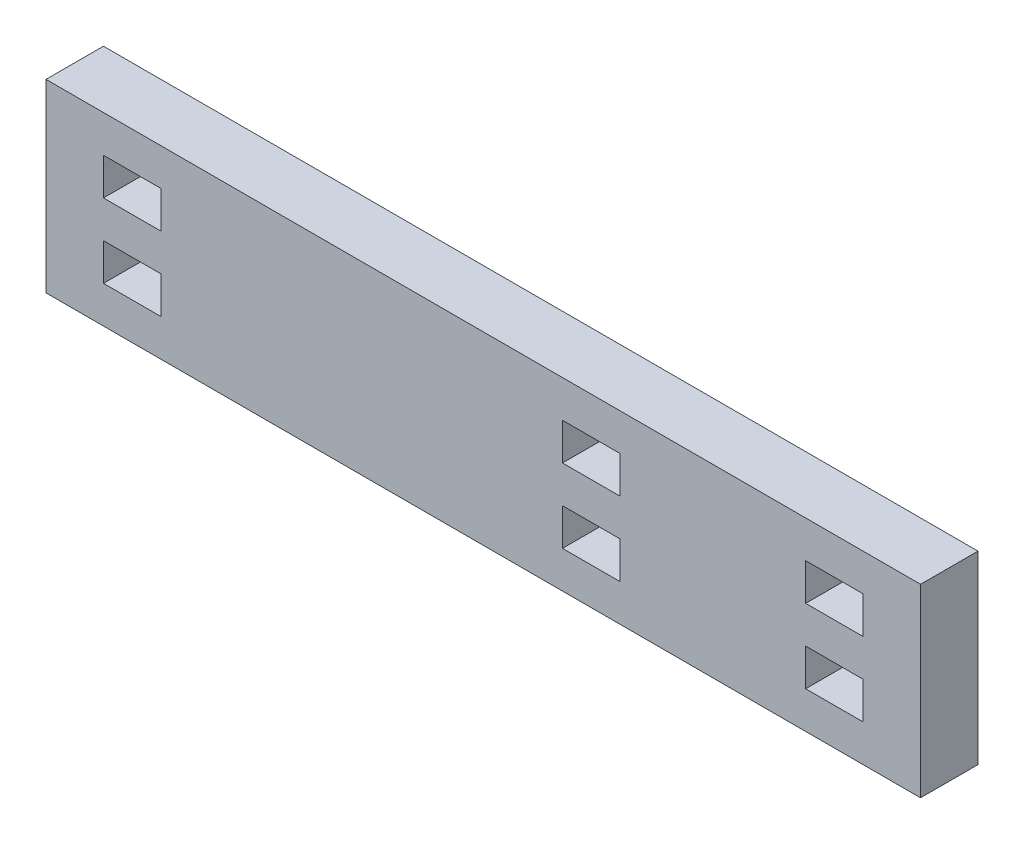
SolidWorks part; units mm, degrees
ref_plane "Front Plane" through (0, 0, 0) normal (0, 0, 1) x (1, 0, 0)
ref_plane "Top Plane" through (0, 0, 0) normal (0, 1, 0) x (1, 0, 0)
ref_plane "Right Plane" through (0, 0, 0) normal (1, 0, 0) x (0, 0, -1)
sketch "Sketch1" plane through (0, 0, 0) normal (0, 0, 1) x (1, 0, 0)
  line L0 (0, 0) -> (0, 16.577)
  line L1 (0, -55) -> (0, 55) construction
  line L2 (0, 16.577) -> (78.4, 16.577)
  line L3 (78.4, 16.577) -> (78.4, 0)
  line L4 (55, 0) -> (-55, 0) construction
  line L5 (78.4, 0) -> (0, 0)
  dimension "D1" = 16.577
  dimension "D2" = 78.4
extrude "Boss-Extrude1" add sketch "Sketch1" along normal blind 5.15
sketch "Sketch2" plane through (0, 0, 5.15) normal (0, 0, 1) x (1, 0, 0)
  line L0 (39.2, 16.577) -> (39.2, -4.7176) construction
  line L1 (5.15, 13.2616) -> (10.3, 13.2616)
  line L2 (5.15, 13.2616) -> (5.15, 9.9462)
  line L3 (5.15, 9.9462) -> (10.3, 9.9462)
  line L4 (10.3, 13.2616) -> (10.3, 9.9462)
  line L5 (5.15, 6.6308) -> (10.3, 6.6308)
  line L6 (5.15, 6.6308) -> (5.15, 3.3154)
  line L7 (5.15, 3.3154) -> (10.3, 3.3154)
  line L8 (10.3, 6.6308) -> (10.3, 3.3154)
  line L9 (78.4, 16.577) -> (0, 16.577) construction
  line L10 (5.695, 16.577) -> (5.695, 13.2616) construction
  line L11 (5.0802, 9.9462) -> (5.0802, 6.6308) construction
  line L12 (4.5423, 3.3154) -> (4.5423, 0) construction
  line L13 (2.8325, 0) -> (-2.8325, 0) construction
  line L14 (0, -2.8325) -> (0, 2.8325) construction
  line L15 (68.1, 6.6308) -> (68.1, 3.3154)
  line L16 (73.25, 3.3154) -> (68.1, 3.3154)
  line L17 (73.25, 6.6308) -> (73.25, 3.3154)
  line L18 (73.25, 6.6308) -> (68.1, 6.6308)
  line L19 (68.1, 13.2616) -> (68.1, 9.9462)
  line L20 (73.25, 9.9462) -> (68.1, 9.9462)
  line L21 (73.25, 13.2616) -> (73.25, 9.9462)
  line L22 (73.25, 13.2616) -> (68.1, 13.2616)
  line L24 (46.3, 13.2616) -> (51.45, 13.2616)
  line L25 (46.3, 13.2616) -> (46.3, 9.9462)
  line L26 (46.3, 9.9462) -> (51.45, 9.9462)
  line L27 (51.45, 13.2616) -> (51.45, 9.9462)
  line L28 (46.3, 6.6308) -> (51.45, 6.6308)
  line L29 (46.3, 6.6308) -> (46.3, 3.3154)
  line L30 (46.3, 3.3154) -> (51.45, 3.3154)
  line L31 (51.45, 6.6308) -> (51.45, 3.3154)
  dimension "D1" = 5.15
  dimension "D2" = 5.15
  dimension "D3" = 36
  dimension "D4" = 5.15
extrude "Cut-Extrude1" cut sketch "Sketch2" against normal blind 5.15
